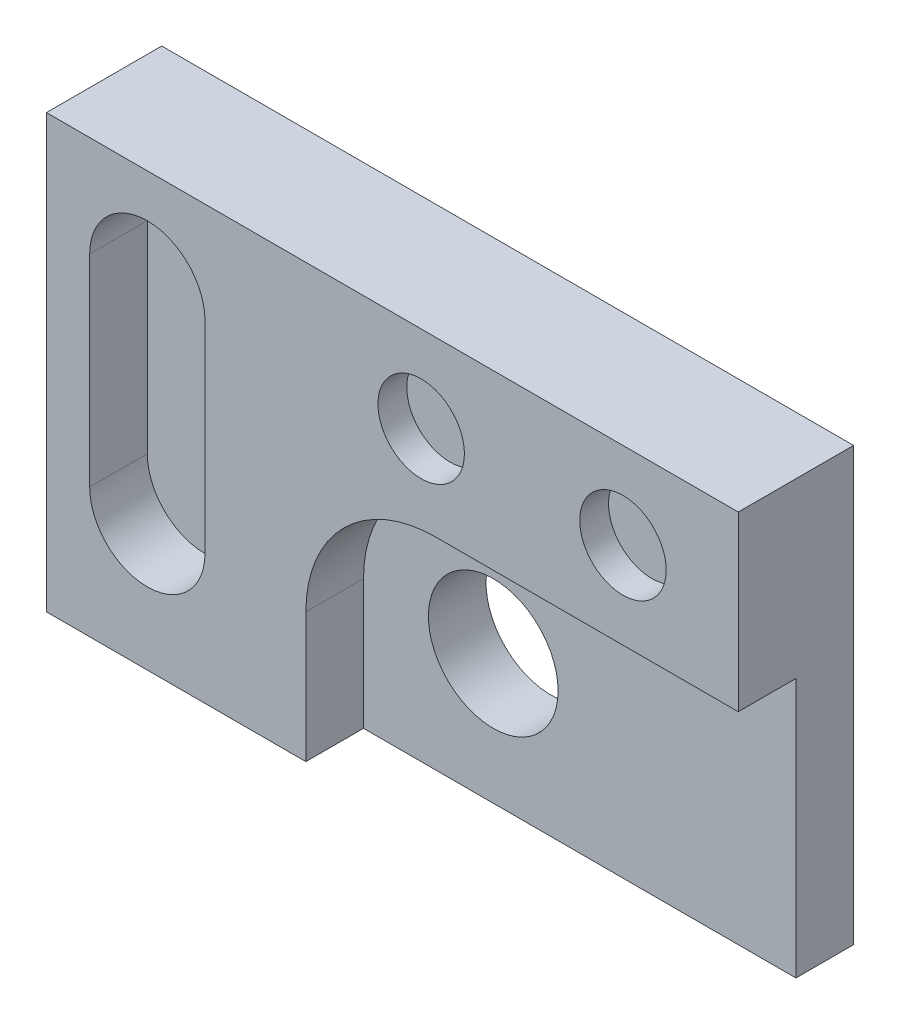
SolidWorks part; units mm, degrees
material "6061-T6 (SS)"
ref_plane "Plan de face" through (0, 0, 0) normal (0, 0, 1) x (1, 0, 0)
ref_plane "Plan de dessus" through (0, 0, 0) normal (0, 1, 0) x (1, 0, 0)
ref_plane "Plan de droite" through (0, 0, 0) normal (1, 0, 0) x (0, 0, -1)
sketch "Esquisse1" plane through (0, 0, 0) normal (0, 0, 1) x (1, 0, 0)
  line L1 (-120, -75) -> (120, -75)
  line L2 (-120, -75) -> (-120, 75)
  line L3 (-120, 75) -> (120, 75)
  line L4 (120, -75) -> (120, 75)
  line L5 (-120, -75) -> (120, 75) construction
  line L6 (-120, 75) -> (120, -75) construction
  point P0 (0, 0)
  dimension "D1" = 150
  dimension "D2" = 240
extrude "Boss.-Extru.1" add sketch "Esquisse1" along normal blind 40
sketch "Esquisse2" plane through (0, 0, 40) normal (0, 0, 1) x (1, 0, 0)
  line L0 (120, 15) -> (15, 15)
  line L1 (120, -75) -> (120, 75) construction
  line L2 (-30, -30) -> (-30, -75)
  line L3 (-120, -75) -> (120, -75) construction
  line L4 (-30, -75) -> (120, -75)
  line L5 (120, -75) -> (120, 15)
  line L6 (-85, -30) -> (-85, 40) construction
  line L7 (-105, -30) -> (-105, 40)
  line L8 (-65, -30) -> (-65, 40)
  line L9 (120, 75) -> (-120, 75) construction
  line L10 (-120, 75) -> (-120, -75) construction
  arc A0 (15, 15) -> (-30, -30) centre (15, -30) ccw
  circle A1 centre (10, 45) radius 15
  circle A2 centre (80, 45) radius 15
  circle A3 centre (15, -30) radius 22.5
  arc A4 (-105, -30) -> (-65, -30) centre (-85, -30) ccw
  arc A5 (-65, 40) -> (-105, 40) centre (-85, 40) ccw
  point P19 (-85, 5)
  line M13 (120, -75) -> (120, 75)
  line M16 (-120, -75) -> (120, -75)
  dimension "D1" = 105
  dimension "D3" = 45
  dimension "D4" = 45
  dimension "D5" = 30
  dimension "D6" = 70
  dimension "D10" = 20
  dimension "D2" = 90
  dimension "D7" = 70
  dimension "D8" = 30
  dimension "D9" = 40
  dimension "D11" = 35
  dimension "D12" = 35
extrude "Enlèv. mat.-Extru.1" cut sketch "Esquisse2" against normal blind 20 contours L8 A5 L7 A4 region at (-85, 5, 40)
extrude "Enlèv. mat.-Extru.2" cut sketch "Esquisse2<3>" against normal blind 10 contours A1 | A2 region at (10, 45, 40) region at (80, 45, 40)
sketch "Esquisse2<3>" plane through (0, 0, 40) normal (0, 0, 1) x (1, 0, 0) same geometry as "Esquisse2"
extrude "Enlèv. mat.-Extru.3" cut sketch "Esquisse2<4>" against normal through all contours A3 region at (15, -30, 40)
sketch "Esquisse2<4>" plane through (0, 0, 40) normal (0, 0, 1) x (1, 0, 0) same geometry as "Esquisse2"
extrude "Enlèv. mat.-Extru.4" cut sketch "Esquisse2<5>" against normal blind 20 contours L0 A0 L2 A3 M16 M13 region at (51.6176, -31.3235, 40)
sketch "Esquisse2<5>" plane through (0, 0, 40) normal (0, 0, 1) x (1, 0, 0) same geometry as "Esquisse2"
